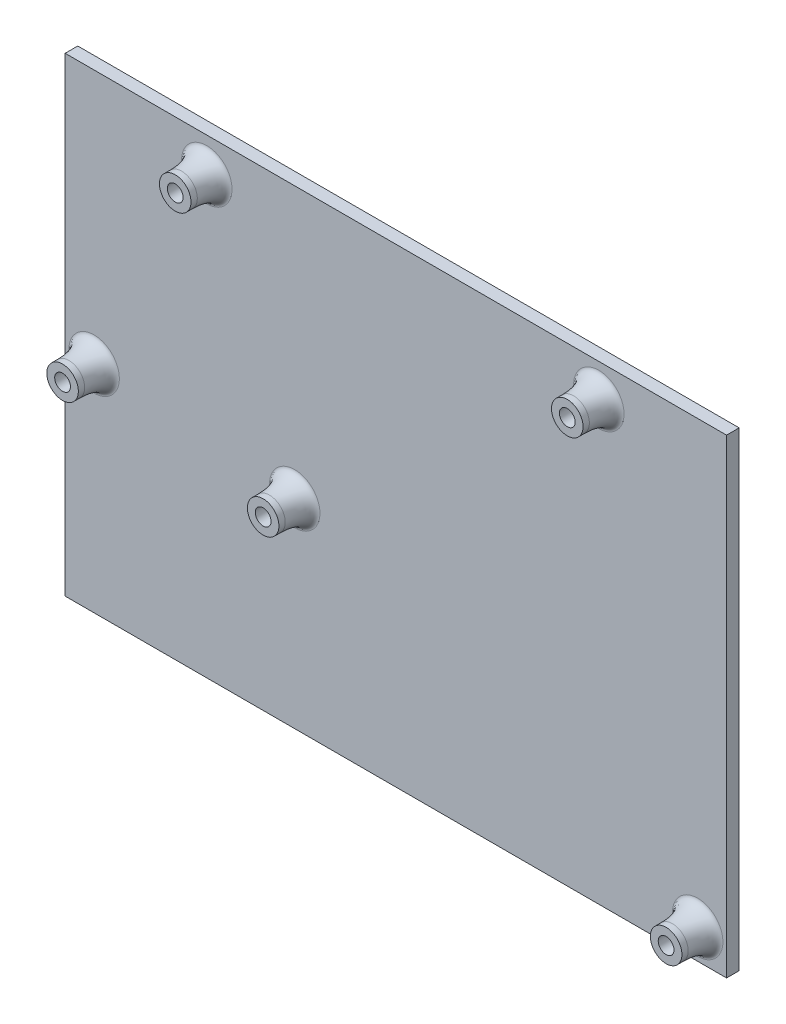
SolidWorks part; units mm, degrees
ref_plane "Front Plane" through (0, 0, 0) normal (0, 0, 1) x (1, 0, 0)
ref_plane "Top Plane" through (0, 0, 0) normal (0, 1, 0) x (1, 0, 0)
ref_plane "Right Plane" through (0, 0, 0) normal (1, 0, 0) x (0, 0, -1)
sketch "Sketch1" plane through (0, 0, 0) normal (0, 0, 1) x (1, 0, 0)
  line L1 (-49.6429, 25.8106) -> (51.2071, 25.8106)
  line L2 (-49.6429, 25.8106) -> (-49.6429, -44.7194)
  line L3 (-49.6429, -44.7194) -> (51.2071, -44.7194)
  line L4 (51.2071, 25.8106) -> (51.2071, -44.7194)
  dimension "D1" = 100.85
  dimension "D2" = 70.53
extrude "Boss-Extrude1" add sketch "Sketch1" along normal blind 2
sketch "Sketch2" plane through (0, 0, 2) normal (0, 0, 1) x (1, 0, 0)
  line L0 (-49.6429, 25.8106) -> (-49.6429, -44.7194) construction
  line L2 (-49.6429, -44.7194) -> (51.2071, -44.7194) construction
  point P0 (-29.1929, 22.3606)
  point P1 (-47.0529, -12.5594)
  point P2 (-15.2529, -15.1494)
  point P3 (48.6271, -42.0494)
  point P4 (32.9571, 22.5906)
  dimension "D1" = 20.45
  dimension "D2" = 67.08
  dimension "D3" = 67.31
  dimension "D4" = 82.6
  dimension "D5" = 2.59
  dimension "D6" = 32.16
  dimension "D7" = 34.39
  dimension "D8" = 29.57
  dimension "D9" = 2.67
  dimension "D10" = 98.27
sketch "Sketch6" plane through (0, 0, 2) normal (0, 0, 1) x (1, 0, 0)
  line L8 (-51.6429, 27.8106) -> (-51.6429, -46.7194)
  line L9 (-51.6429, -46.7194) -> (53.2071, -46.7194)
  line L10 (53.2071, -46.7194) -> (53.2071, 27.8106)
  line L11 (53.2071, 27.8106) -> (-51.6429, 27.8106)
  line L12 (-51.6429, 27.8106) -> (-51.6429, -46.7194)
  line L13 (-51.6429, -46.7194) -> (53.2071, -46.7194)
  line L14 (53.2071, -46.7194) -> (53.2071, 27.8106)
  line L16 (53.2071, 27.8106) -> (-51.6429, 27.8106)
  dimension "D1" = 2
extrude "Boss-Extrude3" add sketch "Sketch6" against normal up to surface (2 mm away) up to face at (0.7821, -9.4544, 0)
sketch "Sketch3" plane through (0, 0, 2) normal (0, 0, 1) x (1, 0, 0)
  circle A0 centre (-29.1929, 22.3606) radius 2.5
  dimension "D1" = 5
extrude "Boss-Extrude2" add sketch "Sketch3" along normal blind 5
hole_wizard "Tap Drill for M3x0.5 Tap1" positions "Sketch4" profile "Sketch5" hole size "M3x0.5" standard "ANSI Metric"
sketch "Sketch4" plane through (0, 0, 7) normal (0, 0, 1) x (1, 0, 0)
  point P0 (-29.1929, 22.3606)
sketch "Sketch5" plane through (-29.1929, 22.3606, 7) normal (1, 0, 0) x (0, -1, 0)
  line L0 (0, 0) -> (0, 10.7511)
  line L1 (0, 10.7511) -> (1.25, 10)
  line L2 (1.25, 10) -> (1.25, 0)
  line L5 (1.25, 0) -> (0, 0)
  line L10 (0, 10.7511) -> (-1.25, 10) construction
  line L11 (0, -6.35) -> (0, 107.95) construction
  dimension "Hole Dia." = 2.5
  dimension "Hole Depth" = 10
  dimension "Drill Angle" = 118
pattern_sketch "Sketch-Pattern1" of "Boss-Extrude2", "Tap Drill for M3x0.5 Tap1" driven by "Sketch2"
fillet "Fillet1" radius 1.5 1 edges at (-26.6929, 22.3606, 2)
